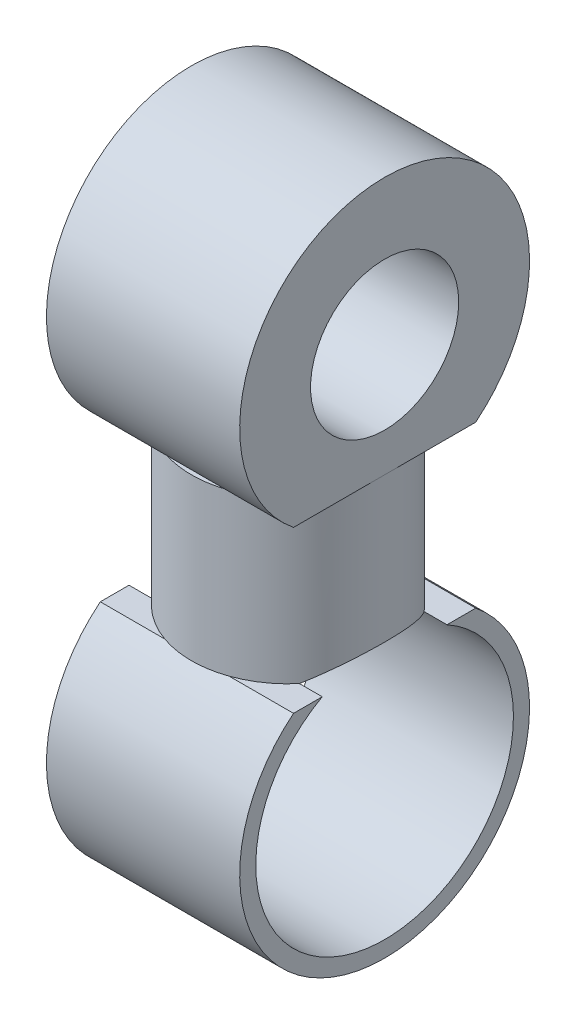
SolidWorks part; units mm, degrees
ref_plane "Front Plane" through (0, 0, 0) normal (0, 0, 1) x (1, 0, 0)
ref_plane "Top Plane" through (0, 0, 0) normal (0, 1, 0) x (1, 0, 0)
ref_plane "Right Plane" through (0, 0, 0) normal (1, 0, 0) x (0, 0, -1)
sketch "Sketch1" plane through (0, 0, 0) normal (0, 1, 0) x (1, 0, 0)
  circle A0 centre (0, 0) radius 3
  dimension "D1" = 6
extrude "crank_body" add sketch "Sketch1" along normal blind 4.5
sketch "Sketch2" plane through (0, 0, 0) normal (0, -1, 0) x (1, 0, 0)
  circle A0 centre (0, 0) radius 1.55
  dimension "D1" = 3.1
sketch "Sketch3" plane through (0, 0, 0) normal (1, 0, 0) x (0, 0, -1)
  line L0 (3, 4.5) -> (-3, 4.5) construction
  line L1 (-3, 4.5) -> (-3, 0) construction
  line L2 (-3, 4.5) -> (3, 4.5)
  line L3 (-3, 4.5) -> (-3, 5)
  line L4 (-3, 5) -> (3, 5)
  line L5 (3, 4.5) -> (3, 5)
  line L6 (3, 0) -> (3, 4.5) construction
  line L7 (-3, 4.5) -> (-3, 0) construction
  circle A0 centre (0, 8.5) radius 4.5
  dimension "D1" = 9
  dimension "D2" = 4
  dimension "D6" = 3
  dimension "D3" = 0.5
  dimension "D4" = 0
  dimension "D5" = 0
extrude "pin_shaft_body" add sketch "Sketch3" along normal blind 3 and the other way blind 3 contours A0 L3 L2 | L3 A0 L5 L4 | L5 A0 L3 L4 | L5 L4 L3 L2 region at (0, 4.6897, 2.6907) region at (0, 4.7628, 0) region at (0, 8.7525, 0)
sketch "Sketch4" plane through (3, 0, 0) normal (1, 0, 0) x (0, 0, -1)
  circle A0 centre (0, 8.5) radius 2.3
  dimension "D1" = 4.6
extrude "pin_shaft" cut sketch "Sketch4" against normal through all
extrude "smoothing_cuts" cut sketch "Sketch1<2>" along normal blind 5 flip side to cut
sketch "Sketch1<2>" plane through (0, 0, 0) normal (0, 1, 0) x (1, 0, 0) same geometry as "Sketch1"
ref_plane "Plane1" through (0, 2.5, 0) normal (0, -1, 0) x (-1, 0, 0)
mirror "Mirror1" about plane through (0, 2.5, 0) normal (0, -1, 0) of "pin_shaft_body", "smoothing_cuts"
sketch "Sketch5" plane through (3, 0, 0) normal (1, 0, 0) x (0, 0, -1)
  circle A0 centre (0, -3.5) radius 4
  dimension "D1" = 8
extrude "Cut-Extrude1" cut sketch "Sketch5" against normal through all
